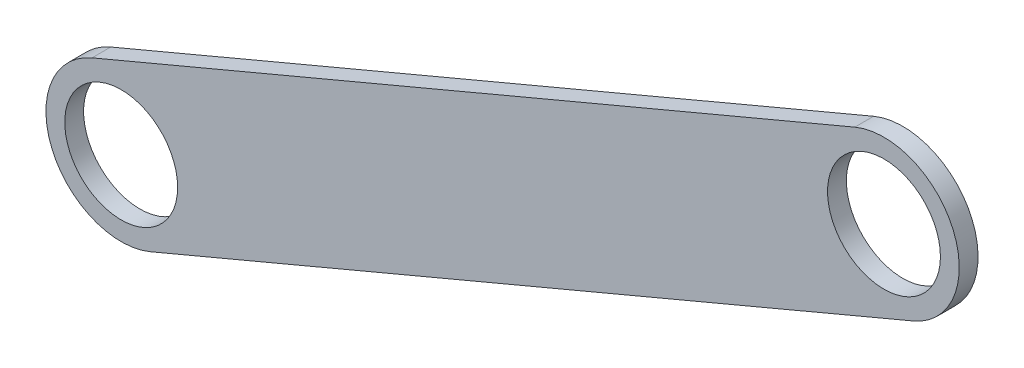
SolidWorks part; units mm, degrees
ref_plane "Front Plane" through (0, 0, 0) normal (0, 0, 1) x (1, 0, 0)
ref_plane "Top Plane" through (0, 0, 0) normal (0, 1, 0) x (1, 0, 0)
ref_plane "Right Plane" through (0, 0, 0) normal (1, 0, 0) x (0, 0, -1)
sketch "Esquisse1" plane through (0, 0, 0) normal (0, 0, 1) x (1, 0, 0)
  line L0 (33.4033, 22.0819) -> (-7.1443, 4.997) construction
  line L1 (34.9564, 18.3957) -> (-5.5912, 1.3109)
  line L2 (31.8501, 25.768) -> (-8.6975, 8.6832)
  arc A0 (34.9564, 18.3957) -> (31.8501, 25.768) centre (33.4033, 22.0819) ccw
  arc A1 (-8.6975, 8.6832) -> (-5.5912, 1.3109) centre (-7.1443, 4.997) ccw
  circle A2 centre (33.4033, 22.0819) radius 3
  circle A3 centre (-7.1443, 4.997) radius 3
  point P4 (13.1295, 13.5394)
  dimension "D2" = 6
  dimension "D3" = 6
  dimension "D1" = 8
base flange "Tôle de base pliée1" sketch "Esquisse1" thickness 1 reverse thickness direction yes parameters "D1"=0.7366
sketch "Bend-Lines1" [suppressed] plane through (0, 0, 0) normal (0, 1, 0) x (1, 0, 0)
sketch "Bounding-Box1" [suppressed] plane through (0, 0, 0) normal (0, 1, 0) x (1, 0, 0)
sheet metal parameters "Sheet-Metal1" thickness 1 parameters "D1"=0.7366
flat pattern "Flat-Pattern1" [suppressed]
sketch "Bend-Lines2" plane through (0, 0, 0) normal (0, 1, 0) x (1, 0, 0)
sketch3d "Bounding-Box2" [suppressed]
  line L0 (42.6806, -22.3241, 0) -> (-5.2393, -2.133, 0) construction
  line L1 (45.7869, -14.9518, 0) -> (-2.1329, 5.2393, 0) construction
  line L2 (42.6806, -22.3241, 0) -> (45.7869, -14.9518, 0) construction
  line L3 (-5.2393, -2.133, 0) -> (-2.1329, 5.2393, 0) construction
